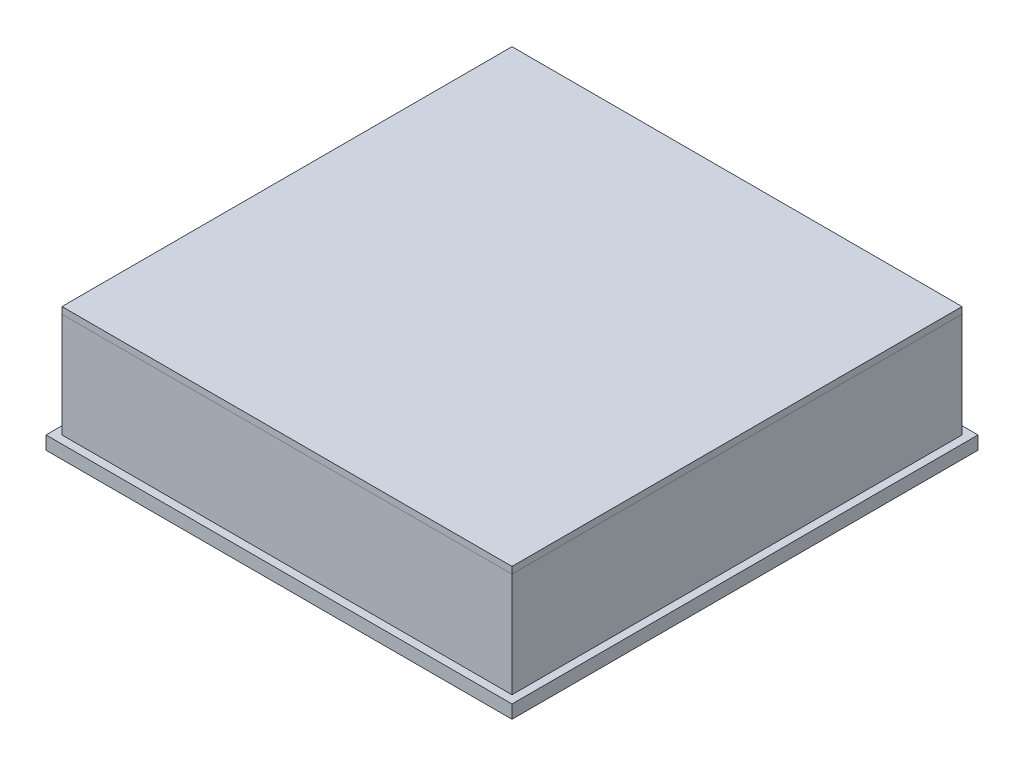
SolidWorks part; units mm, degrees
ref_plane "Front Plane" through (0, 0, 0) normal (0, 0, 1) x (1, 0, 0)
ref_plane "Top Plane" through (0, 0, 0) normal (0, 1, 0) x (1, 0, 0)
ref_plane "Right Plane" through (0, 0, 0) normal (1, 0, 0) x (0, 0, -1)
sketch "Sketch2" plane through (0, 0, 0) normal (0, 1, 0) x (1, 0, 0)
  line L0 (-4304.792, -4304.792) -> (-4304.792, 4304.792)
  line L1 (3999.992, -3999.992) -> (-3999.992, -3999.992)
  line L2 (3999.992, -3999.992) -> (3999.992, 3999.992)
  line L3 (3999.992, 3999.992) -> (-3999.992, 3999.992)
  line L4 (-3999.992, -3999.992) -> (-3999.992, 3999.992)
  line L5 (3999.992, -3999.992) -> (-3999.992, 3999.992) construction
  line L6 (3999.992, 3999.992) -> (-3999.992, -3999.992) construction
  line L7 (4304.792, 4304.792) -> (-4304.792, 4304.792)
  line L8 (4304.792, -4304.792) -> (4304.792, 4304.792)
  line L9 (4304.792, -4304.792) -> (-4304.792, -4304.792)
  point P0 (0, 0)
  dimension "D1" = 7999.984
  dimension "D2" = 7999.984
  dimension "D3" = 304.8
extrude "Boss-Extrude1" add sketch "Sketch2" along normal blind 1999.996
sketch "Sketch3" plane through (0, 0, 0) normal (0, -1, 0) x (1, 0, 0)
  line L0 (-4304.792, -4304.792) -> (-4304.792, 4304.792) construction
  line L1 (-4304.792, -4304.792) -> (-4304.792, 4304.792)
  line L2 (4304.792, -4304.792) -> (-4304.792, -4304.792) construction
  line L3 (4304.792, 4304.792) -> (4304.792, -4304.792) construction
  line L4 (-4304.792, 4304.792) -> (4304.792, 4304.792) construction
  line L5 (4304.792, -4304.792) -> (-4304.792, -4304.792)
  line L6 (4304.792, 4304.792) -> (4304.792, -4304.792)
  line L7 (-4304.792, 4304.792) -> (4304.792, 4304.792)
extrude "Boss-Extrude2" add sketch "Sketch3" along normal blind 152.4
sketch "Sketch6" plane through (0, 0, 0) normal (0, 1, 0) x (1, 0, 0)
  line L0 (0, 0) -> (-3999.992, 3999.992) construction
  line L6 (-3999.992, 1656.8509) -> (-1656.8509, 1656.8509) construction
  line L7 (-3999.992, 3999.992) -> (-3999.992, -3999.992) construction
  line L19 (-1656.8509, 1656.8509) -> (-1656.8509, 3999.992) construction
  line L20 (3999.992, 3999.992) -> (-3999.992, 3999.992) construction
  line L22 (-1656.8509, 1656.8509) -> (0, 0) construction
  line L24 (1809.2509, 1504.4509) -> (1809.2509, 1809.2509)
  line L25 (-1504.4509, 1809.2509) -> (-1809.2509, 1809.2509)
  line L29 (-1504.4509, 1809.2509) -> (-1504.4509, 1504.4509)
  line L30 (-1504.4509, 1504.4509) -> (-1809.2509, 1504.4509)
  line L31 (-1809.2509, 1809.2509) -> (-1809.2509, 1504.4509)
  line L32 (-1504.4509, 1809.2509) -> (-1809.2509, 1504.4509) construction
  line L33 (-1504.4509, 1504.4509) -> (-1809.2509, 1809.2509) construction
  line L34 (1809.2509, 1809.2509) -> (1504.4509, 1809.2509)
  line L35 (1504.4509, 1504.4509) -> (1504.4509, 1809.2509)
  line L36 (1809.2509, 1504.4509) -> (1504.4509, 1504.4509)
  line L37 (1504.4509, -1809.2509) -> (1809.2509, -1809.2509)
  line L38 (1809.2509, -1809.2509) -> (1809.2509, -1504.4509)
  line L39 (1504.4509, -1504.4509) -> (1809.2509, -1504.4509)
  line L40 (1504.4509, -1809.2509) -> (1504.4509, -1504.4509)
  line L41 (-1809.2509, -1504.4509) -> (-1809.2509, -1809.2509)
  line L42 (-1809.2509, -1809.2509) -> (-1504.4509, -1809.2509)
  line L43 (-1504.4509, -1504.4509) -> (-1504.4509, -1809.2509)
  line L44 (-1809.2509, -1504.4509) -> (-1504.4509, -1504.4509)
  point P30 (0, 0)
  dimension "D1" = 304.8
extrude "Boss-Extrude5" add sketch "Sketch6" along normal up to surface (1999.996 mm away) contours L25 L31 L30 L29 | L36 L24 L34 L35 | L40 L37 L38 L39 | L44 L41 L42 L43 region at (1656.8509, 0, -1656.8509) region at (-1656.8509, 0, -1656.8509) region at (1656.8509, 0, 1656.8509) region at (-1656.8509, 0, 1656.8509) up to face at (0, 1999.996, 0)
sketch "Sketch7" plane through (0, 1999.996, 0) normal (0, 1, 0) x (1, 0, 0)
  line L1 (4304.792, -4304.792) -> (-4304.792, -4304.792)
  line L2 (4304.792, -4304.792) -> (4304.792, 4304.792)
  line L3 (4304.792, 4304.792) -> (-4304.792, 4304.792)
  line L4 (-4304.792, -4304.792) -> (-4304.792, 4304.792)
  line L5 (4304.792, -4304.792) -> (-4304.792, 4304.792) construction
  line L6 (4304.792, 4304.792) -> (-4304.792, -4304.792) construction
  point P0 (0, 0)
extrude "Boss-Extrude6" add sketch "Sketch7" along normal blind 127 separate body
sketch "Sketch4" plane through (0, -152.4, 0) normal (0, -1, 0) x (1, 0, 0)
  line L30 (-4457.192, 4457.192) -> (-4457.192, -4457.192)
  line L31 (-4457.192, -4457.192) -> (4457.192, -4457.192)
  line L32 (4457.192, -4457.192) -> (4457.192, 4457.192)
  line L33 (4457.192, 4457.192) -> (-4457.192, 4457.192)
  line L34 (-4457.192, 4457.192) -> (-4457.192, -4457.192)
  line L35 (-4457.192, -4457.192) -> (4457.192, -4457.192)
  line L36 (4457.192, -4457.192) -> (4457.192, 4457.192)
  line L37 (4457.192, 4457.192) -> (-4457.192, 4457.192)
  line L43 (3847.592, 3847.592) -> (-3847.592, 3847.592)
  line L44 (-3847.592, 3847.592) -> (-3847.592, -3847.592)
  line L45 (-3847.592, -3847.592) -> (3847.592, -3847.592)
  line L46 (3847.592, -3847.592) -> (3847.592, 3847.592)
  line L47 (3847.592, 3847.592) -> (-3847.592, 3847.592)
  line L48 (-3847.592, 3847.592) -> (-3847.592, -3847.592)
  line L49 (-3847.592, -3847.592) -> (3847.592, -3847.592)
  line L50 (3847.592, -3847.592) -> (3847.592, 3847.592)
  dimension "D1" = 152.4
  dimension "D2" = 152.4
extrude "Boss-Extrude3" [suppressed] add sketch "Sketch4" along normal blind 304.8
sketch "Sketch8" plane through (0, 0, -1504.4509) normal (0, 0, 1) x (1, 0, 0)
  line L0 (-3999.992, 1999.996) -> (-3999.992, 0) construction
  line L1 (3999.992, 1999.996) -> (-3999.992, 1999.996)
  line L2 (3999.992, 1999.996) -> (3999.992, 1753.1524)
  line L3 (3999.992, 1753.1524) -> (-3999.992, 1753.1524)
  line L4 (-3999.992, 1999.996) -> (-3999.992, 1753.1524)
  line L5 (3999.992, 1999.996) -> (-3999.992, 1753.1524) construction
  line L6 (3999.992, 1753.1524) -> (-3999.992, 1999.996) construction
  line L7 (3999.992, 1999.996) -> (-3999.992, 1999.996) construction
  line L8 (3999.992, 1999.996) -> (-3999.992, 1999.996)
  point P0 (0, 1876.5742)
ref_axis "Axis1" through (0, 0, 0) along (0, 1, 0)
sketch "Right Plane Rebar" [suppressed] plane through (0, 0, 0) normal (1, 0, 0) x (0, 0, -1)
  line L0 (4234.942, 2063.496) -> (4234.942, -393.7)
  line L1 (-4457.192, -457.2) -> (4457.192, -457.2) construction
  line L2 (4069.842, 2044.446) -> (4069.842, 50.8)
  line L3 (4222.242, 1314.196) -> (4222.242, 1923.796)
  line L4 (-4304.792, 1999.996) -> (-4304.792, -152.4)
  line L5 (-4304.792, -152.4) -> (4304.792, -152.4)
  line L6 (4304.792, -152.4) -> (4304.792, 1999.996)
  line L7 (4304.792, 1999.996) -> (-4304.792, 1999.996)
  line L8 (-4304.792, 1999.996) -> (-4304.792, -152.4)
  line L10 (4304.792, -152.4) -> (4304.792, 1999.996)
  line L12 (4095.242, 2050.796) -> (3485.642, 2050.796)
  line L13 (4095.242, 2063.496) -> (-4095.242, 2063.496)
  line L14 (0, 1421.3078) -> (0, -1421.3078) construction
  line L15 (3955.542, -88.9) -> (-3955.542, -88.9)
  line L16 (3999.992, 1999.996) -> (-3999.992, 1999.996)
  line L17 (3999.992, 1999.996) -> (-3999.992, 1999.996)
  line L18 (-4304.792, 2126.996) -> (4304.792, 2126.996) construction
  line L19 (3999.992, 0) -> (3999.992, 1999.996)
  line L20 (-3999.992, 0) -> (3999.992, 0)
  line L21 (-3999.992, 1999.996) -> (-3999.992, 0)
  line L27 (3999.992, 0) -> (3999.992, 1999.996)
  line L28 (-3999.992, 0) -> (3999.992, 0)
  line L29 (-3999.992, 1999.996) -> (-3999.992, 0)
  line L32 (4082.542, 660.4) -> (4082.542, 50.8)
  line L33 (3955.542, -76.2) -> (3345.942, -76.2)
  line L37 (-4304.792, -152.4) -> (4304.792, -152.4)
  line L38 (4304.792, 1999.996) -> (-4304.792, 1999.996)
  arc A0 (4222.242, 1923.796) -> (4095.242, 2050.796) centre (4095.242, 1923.796) ccw
  arc A1 (3955.542, -76.2) -> (4082.542, 50.8) centre (3955.542, 50.8) ccw
  point P23 (4222.242, 2050.796)
  point P30 (0, 2063.496)
  point P41 (0, -88.9)
  dimension "D12" = 127
  dimension "D19" = 127
  dimension "D5" = 69.85
  dimension "Vertical Rebar Outer" = 2457.196
  dimension "D4" = 63.5
  dimension "D8" = 69.85
  dimension "D11" = 12.7
  dimension "D10" = 6.35
  dimension "D13" = 609.6
  dimension "D14" = 609.6
  dimension "D15" = 12.7
  dimension "D17" = 12.7
  dimension "D18" = 12.7
  dimension "D7" = 609.6
  dimension "D20" = 609.6
  dimension "Vertical Rebar Inner" = 1993.646
  dimension "Lid Rebar Length" = 8190.484
  dimension "Base Rebar Length" = 7911.084
  dimension "D3" = 63.5
  dimension "D6" = 63.5
  dimension "D1" = 0
  dimension "D2" = 0
sketch "Front Plane Rebar" [suppressed] plane through (0, 0, 0) normal (0, 0, 1) x (1, 0, 0)
  line L0 (4247.642, 2063.496) -> (4247.642, -393.7)
  line L1 (3999.992, 1999.996) -> (3999.992, 0) construction
  line L2 (4057.142, 2031.746) -> (4057.142, 63.5)
  line L3 (4234.942, 1301.496) -> (4234.942, 1911.096)
  line L4 (-4304.792, 2126.996) -> (4304.792, 2126.996) construction
  line L5 (4457.192, -457.2) -> (-4457.192, -457.2) construction
  line L6 (4457.192, -152.4) -> (-4457.192, -152.4) construction
  line L7 (4304.792, 2126.996) -> (-4304.792, 2126.996) construction
  line L8 (-4304.792, 1999.996) -> (-4304.792, -152.4)
  line L9 (-4304.792, -152.4) -> (4304.792, -152.4)
  line L10 (4304.792, -152.4) -> (4304.792, 1999.996)
  line L12 (4107.942, 2038.096) -> (3498.342, 2038.096)
  line L13 (4107.942, 2050.796) -> (-4107.942, 2050.796)
  line L15 (3942.842, -76.2) -> (-3942.842, -76.2)
  line L17 (3999.992, 1999.996) -> (-3999.992, 1999.996)
  line L19 (-3999.992, 0) -> (3999.992, 0)
  line L20 (3999.992, 0) -> (3999.992, 1999.996)
  line L21 (3999.992, 1999.996) -> (-3999.992, 1999.996)
  line L22 (-3999.992, 1999.996) -> (-3999.992, 0)
  line L23 (-3999.992, 0) -> (3999.992, 0)
  line L27 (3999.992, 0) -> (3999.992, 1999.996)
  line L28 (-3999.992, 0) -> (3999.992, 0)
  line L29 (-3999.992, 1999.996) -> (-3999.992, 0)
  line L32 (4069.842, 673.1) -> (4069.842, 63.5)
  line L33 (3942.842, -63.5) -> (3333.242, -63.5)
  line L34 (3999.992, 0) -> (3999.992, 1999.996)
  line L35 (3999.992, 1999.996) -> (-3999.992, 1999.996)
  line L36 (-3999.992, 1999.996) -> (-3999.992, 0)
  line L37 (4304.792, -152.4) -> (4304.792, 1999.996)
  line L38 (4304.792, 1999.996) -> (-4304.792, 1999.996)
  line L39 (-4304.792, -152.4) -> (4304.792, -152.4)
  line L40 (-4304.792, 1999.996) -> (-4304.792, -152.4)
  line L41 (4304.792, 1999.996) -> (-4304.792, 1999.996)
  line L42 (4304.792, -152.4) -> (4304.792, 1999.996)
  line L44 (-4304.792, 1999.996) -> (-4304.792, -152.4)
  line L45 (4304.792, 1999.996) -> (-4304.792, 1999.996)
  line L48 (-4304.792, -152.4) -> (4304.792, -152.4)
  arc A0 (4234.942, 1911.096) -> (4107.942, 2038.096) centre (4107.942, 1911.096) ccw
  arc A1 (3942.842, -63.5) -> (4069.842, 63.5) centre (3942.842, 63.5) ccw
  point P23 (4234.942, 2038.096)
  point P30 (0, 2050.796)
  point P41 (0, -76.2)
  dimension "D13" = 609.6
  dimension "D12" = 127
  dimension "D19" = 127
  dimension "D3" = 76.2
  dimension "D4" = 63.5
  dimension "D5" = 57.15
  dimension "D6" = 0
  dimension "D7" = 609.6
  dimension "D8" = 57.15
  dimension "Vertical Rebar Outer" = 2457.196
  dimension "D9" = 0
  dimension "D10" = 6.35
  dimension "D11" = 12.7
  dimension "D14" = 609.6
  dimension "D15" = 12.7
  dimension "D16" = 76.2
  dimension "D17" = 12.7
  dimension "D18" = 12.7
  dimension "D20" = 609.6
  dimension "D21" = 63.5
  dimension "Vertical Rebar Inner" = 1968.246
  dimension "Lid Rebar Length" = 8215.884
  dimension "Base Rebar Length" = 7885.684
sketch "Sketch9" [suppressed] plane through (0, -152.4, 0) normal (0, 1, 0) x (1, 0, 0)
  line L0 (-4260.342, 4393.692) -> (-4260.342, -4393.692)
  line L1 (-4457.192, -4457.192) -> (-4457.192, 4457.192) construction
  line L2 (-4457.192, -4457.192) -> (-4457.192, 4457.192)
  line L3 (-3847.592, -3847.592) -> (-3847.592, 3847.592) construction
  line L4 (-3847.592, -3847.592) -> (-3847.592, 3847.592)
  line L5 (-4457.192, 4457.192) -> (4457.192, 4457.192) construction
  line L6 (4457.192, -4457.192) -> (-4457.192, -4457.192) construction
  line L7 (-4044.442, 4152.392) -> (-4044.442, -4152.392)
  line L8 (4393.692, 4260.342) -> (-4393.692, 4260.342)
  line L9 (4152.392, 4044.442) -> (-4152.392, 4044.442)
  line L10 (4260.342, -4393.692) -> (4260.342, 4393.692)
  line L11 (4044.442, -4152.392) -> (4044.442, 4152.392)
  line L12 (-4393.692, -4260.342) -> (4393.692, -4260.342)
  line L13 (-4152.392, -4044.442) -> (4152.392, -4044.442)
  point P27 (0, 0)
  dimension "D1" = 196.85
  dimension "D2" = 63.5
  dimension "D3" = 63.5
  dimension "D4" = 196.85
  dimension "D5" = 304.8
  dimension "D6" = 304.8
  dimension "D7" = 8787.384
  dimension "D8" = 8304.784
  dimension "D9" = 4
sketch "Sketch11" [suppressed] plane through (0, 0, -1504.4509) normal (0, 0, 1) x (1, 0, 0)
  line L0 (-1745.7509, 2063.496) -> (-1745.7509, -88.9)
  line L1 (-1745.7509, 2063.496) -> (-1745.7509, 1930.146)
  line L2 (-4304.792, 2126.996) -> (4304.792, 2126.996) construction
  line L4 (4457.192, -152.4) -> (-4457.192, -152.4) construction
  line L5 (-1745.7509, -88.9) -> (-1745.7509, 44.45)
  line L6 (-1504.4509, 0) -> (-1504.4509, 1999.996)
  line L7 (-1504.4509, 1999.996) -> (-1809.2509, 1999.996)
  line L8 (-1809.2509, 1999.996) -> (-1809.2509, 0)
  line L9 (-1809.2509, 0) -> (-1504.4509, 0)
  line L10 (-1504.4509, 0) -> (-1504.4509, 1999.996)
  line L11 (-1504.4509, 1999.996) -> (-1809.2509, 1999.996)
  line L12 (-1809.2509, 1999.996) -> (-1809.2509, 0)
  line L13 (-1809.2509, 0) -> (-1504.4509, 0)
  dimension "D2" = 63.5
  dimension "D3" = 133.35
  dimension "D4" = 63.5
  dimension "D5" = 63.5
  dimension "D6" = 133.35
  dimension "D7" = 1885.696
  dimension "D1" = 0
sketch "Sketch13" [suppressed] plane through (0, 2126.996, 0) normal (0, 1, 0) x (1, 0, 0)
  line L0 (-4222.242, 4253.992) -> (-4222.242, -4253.992)
  line L1 (-4304.792, 4304.792) -> (-4304.792, -4304.792) construction
  line L2 (-4304.792, 4304.792) -> (4304.792, 4304.792) construction
  line L3 (4304.792, -4304.792) -> (-4304.792, -4304.792) construction
  dimension "D1" = 82.55
  dimension "D2" = 50.8
  dimension "D3" = 50.8
  dimension "D4" = 8507.984
ref_plane "Plane1" through (-4304.792, 1999.996, -4304.792) normal (0, -1, 0) x (-1, 0, 0)
sketch "Sketch14" plane through (0, 0, 0) normal (0, 1, 0) x (1, 0, 0)
  line L0 (-4304.792, 4304.792) -> (-4304.792, -4304.792) construction
  line L1 (4457.192, -4457.192) -> (-4457.192, -4457.192)
  line L2 (4457.192, -4457.192) -> (4457.192, 4457.192)
  line L3 (4457.192, 4457.192) -> (-4457.192, 4457.192)
  line L4 (-4457.192, -4457.192) -> (-4457.192, 4457.192)
  line L5 (4457.192, -4457.192) -> (-4457.192, 4457.192) construction
  line L6 (4457.192, 4457.192) -> (-4457.192, -4457.192) construction
  line L7 (4304.792, 4304.792) -> (-4304.792, 4304.792) construction
  point P0 (0, 0)
  dimension "D1" = 152.4
  dimension "D2" = 152.4
extrude "Boss-Extrude7" add sketch "Sketch14" against normal blind 254
sketch "Sketch15" plane through (0, 2126.996, 0) normal (0, 1, 0) x (1, 0, 0)
  line L0 (4304.792, -4304.792) -> (4304.792, 4304.792) construction
  line L1 (-3999.992, -3999.992) -> (3999.992, -3999.992)
  line L2 (-3999.992, -3999.992) -> (-3999.992, 3999.992)
  line L3 (-3999.992, 3999.992) -> (3999.992, 3999.992)
  line L4 (3999.992, -3999.992) -> (3999.992, 3999.992)
  line L5 (-3999.992, -3999.992) -> (3999.992, 3999.992) construction
  line L6 (-3999.992, 3999.992) -> (3999.992, -3999.992) construction
  line L7 (4304.792, 4304.792) -> (-4304.792, 4304.792) construction
  line L9 (3085.592, 3491.992) -> (3999.992, 3491.992)
  line L10 (3085.592, 3491.992) -> (3085.592, 2577.592)
  line L11 (3085.592, 2577.592) -> (3999.992, 2577.592)
  line L12 (3999.992, 3491.992) -> (3999.992, 2577.592)
  line L13 (3085.592, 3491.992) -> (3999.992, 2577.592) construction
  line L14 (3085.592, 2577.592) -> (3999.992, 3491.992) construction
  point P0 (0, 0)
  point P10 (3542.792, 3034.792)
  dimension "D1" = 304.8
  dimension "D2" = 304.8
  dimension "D3" = 914.4
  dimension "D4" = 914.4
  dimension "D5" = 965.2
equation "\"Contact Length\"= 24"
equation "\"Rebar Bend Radius\"= 5"
equation "\"D13@Right Plane Rebar\" = \"Contact Length\""
